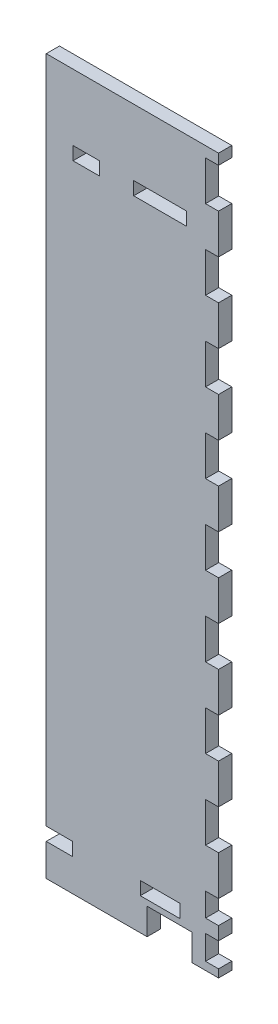
SolidWorks part; units mm, degrees
material "Balsa"
ref_plane "Plan de face" through (0, 0, 0) normal (0, 0, 1) x (1, 0, 0)
ref_plane "Plan de dessus" through (0, 0, 0) normal (0, 1, 0) x (1, 0, 0)
ref_plane "Plan de droite" through (0, 0, 0) normal (1, 0, 0) x (0, 0, -1)
sketch "Esquisse1" plane through (0, 0, 0) normal (0, 0, 1) x (1, 0, 0)
  line L1 (65.1211, 0) -> (0, 0)
  line L2 (65.1211, 0) -> (65.1211, 270)
  line L3 (65.1211, 270) -> (0, 270)
  line L4 (0, 0) -> (0, 270)
  dimension "D1" = 270
  dimension "D2" = 65.1211
extrude "Boss.-Extru.1" add sketch "Esquisse1" against normal blind 5
sketch "Esquisse2" plane through (0, 0, 0) normal (0, 0, 1) x (1, 0, 0)
  line L0 (0, 270) -> (0, 0) construction
  line L1 (0, 17.15) -> (10, 17.15)
  line L2 (0, 17.15) -> (0, 12.15)
  line L3 (0, 12.15) -> (10, 12.15)
  line L4 (10, 17.15) -> (10, 12.15)
  line L5 (65.1211, 0) -> (65.1211, 270) construction
  line L6 (50.5493, 17.15) -> (35.5493, 17.15)
  line L7 (50.5493, 17.15) -> (50.5493, 12.15)
  line L8 (50.5493, 12.15) -> (35.5493, 12.15)
  line L9 (35.5493, 17.15) -> (35.5493, 12.15)
  line L10 (65.1211, 12.15) -> (60.2011, 12.15)
  line L11 (65.1211, 12.15) -> (65.1211, 3)
  line L12 (65.1211, 3) -> (60.2011, 3)
  line L13 (60.2011, 12.15) -> (60.2011, 3)
  line L14 (0, 0) -> (65.1211, 0) construction
  line L15 (65.1211, 0) -> (65.1211, 270) construction
  line L16 (65.1211, 17.15) -> (60.2011, 17.15)
  line L17 (65.1211, 17.15) -> (65.1211, 26)
  line L18 (65.1211, 26) -> (60.2011, 26)
  line L19 (60.2011, 17.15) -> (60.2011, 26)
  line L20 (65.1211, 270) -> (0, 270) construction
  line L21 (65.1211, 266) -> (60.2011, 266)
  line L22 (65.1211, 266) -> (65.1211, 251)
  line L23 (65.1211, 251) -> (60.2011, 251)
  line L24 (60.2011, 266) -> (60.2011, 251)
  line L25 (65.1211, 236) -> (60.2011, 236)
  line L26 (65.1211, 236) -> (65.1211, 221)
  line L27 (65.1211, 221) -> (60.2011, 221)
  line L28 (60.2011, 236) -> (60.2011, 221)
  line L29 (65.1211, 206) -> (60.2011, 206)
  line L30 (65.1211, 206) -> (65.1211, 191)
  line L31 (65.1211, 191) -> (60.2011, 191)
  line L32 (60.2011, 206) -> (60.2011, 191)
  line L33 (65.1211, 176) -> (60.2011, 176)
  line L34 (65.1211, 176) -> (65.1211, 161)
  line L35 (65.1211, 161) -> (60.2011, 161)
  line L36 (60.2011, 176) -> (60.2011, 161)
  line L37 (65.1211, 146) -> (60.2011, 146)
  line L38 (65.1211, 146) -> (65.1211, 131)
  line L39 (65.1211, 131) -> (60.2011, 131)
  line L40 (60.2011, 146) -> (60.2011, 131)
  line L41 (65.1211, 116) -> (60.2011, 116)
  line L42 (65.1211, 116) -> (65.1211, 101)
  line L43 (65.1211, 101) -> (60.2011, 101)
  line L44 (60.2011, 116) -> (60.2011, 101)
  line L45 (65.1211, 86) -> (60.2011, 86)
  line L46 (65.1211, 86) -> (65.1211, 71)
  line L47 (65.1211, 71) -> (60.2011, 71)
  line L48 (60.2011, 86) -> (60.2011, 71)
  line L49 (65.1211, 56) -> (60.2011, 56)
  line L50 (65.1211, 56) -> (65.1211, 41)
  line L51 (65.1211, 41) -> (60.2011, 41)
  line L52 (60.2011, 56) -> (60.2011, 41)
  line L54 (10.1211, 245) -> (20.1211, 245)
  line L55 (10.1211, 245) -> (10.1211, 240)
  line L56 (10.1211, 240) -> (20.1211, 240)
  line L57 (20.1211, 245) -> (20.1211, 240)
  line L59 (33.0493, 240) -> (53.0493, 240)
  line L60 (33.0493, 240) -> (33.0493, 245)
  line L61 (33.0493, 245) -> (53.0493, 245)
  line L62 (53.0493, 240) -> (53.0493, 245)
  dimension "D1" = 3
  dimension "D2" = 4.92
  dimension "D3" = 9.15
  dimension "D4" = 12.15
  dimension "D5" = 5
  dimension "D6" = 5
  dimension "D7" = 15
  dimension "D8" = 5
  dimension "D9" = 15
  dimension "D10" = 4
  dimension "D12" = 30
  dimension "D13" = 10
  dimension "D14" = 20
  dimension "D15" = 55
  dimension "D16" = 5
  dimension "D17" = 12.0718
  dimension "D18" = 25
  dimension "D11" = 8
extrude "Enlèv. mat.-Extru.1" cut sketch "Esquisse2" against normal blind 5
sketch "Esquisse3" plane through (0, 0, 0) normal (0, 0, 1) x (1, 0, 0)
  line L0 (0, 0) -> (65.1211, 0) construction
  line L1 (38.1211, 0) -> (55.1211, 0)
  line L2 (38.1211, 0) -> (38.1211, 10)
  line L3 (38.1211, 10) -> (55.1211, 10)
  line L4 (55.1211, 0) -> (55.1211, 10)
  line L5 (65.1211, 0) -> (65.1211, 3) construction
  dimension "D1" = 10
  dimension "D2" = 10
  dimension "D3" = 17
extrude "Enlèv. mat.-Extru.2" cut sketch "Esquisse3" against normal blind 5
